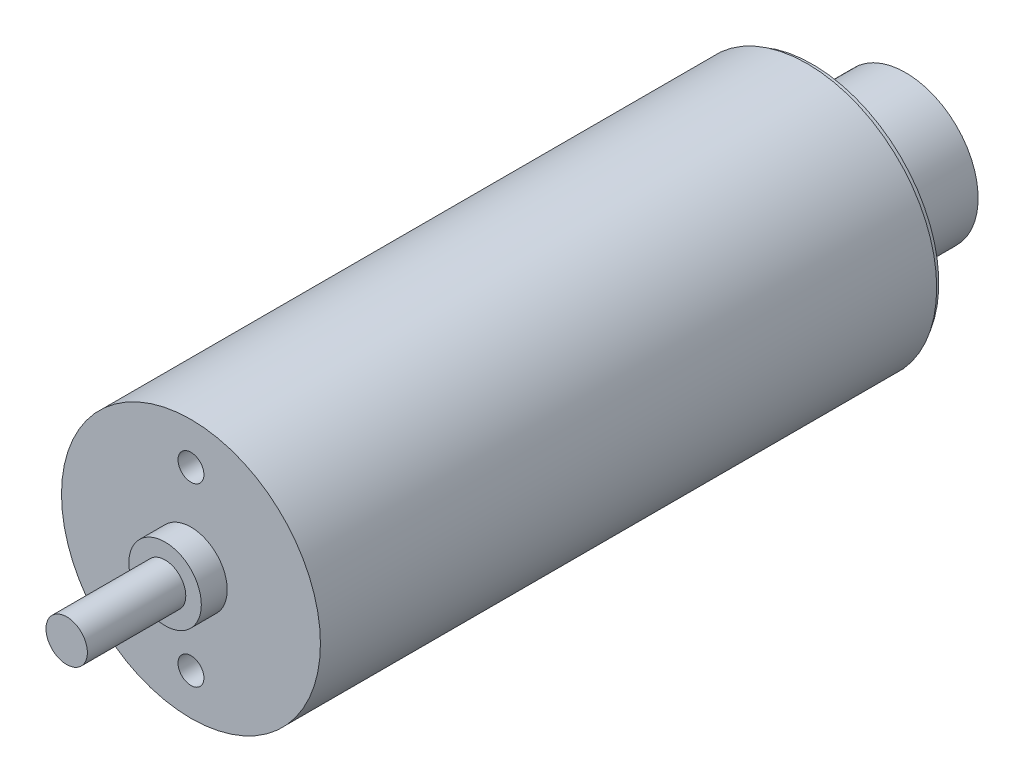
SolidWorks part; units mm, degrees
material "AISI 304"
ref_plane "Front Plane" through (0, 0, 0) normal (0, 0, 1) x (1, 0, 0)
ref_plane "Top Plane" through (0, 0, 0) normal (0, 1, 0) x (1, 0, 0)
ref_plane "Right Plane" through (0, 0, 0) normal (1, 0, 0) x (0, 0, -1)
sketch "Sketch1" plane through (0, 0, 0) normal (0, 0, 1) x (1, 0, 0)
  circle A0 centre (0, 0) radius 12.5
  dimension "D1" = 25
extrude "Boss-Extrude1" add sketch "Sketch1" against normal blind 60
sketch "Sketch2" plane through (0, 0, 0) normal (0, 0, 1) x (1, 0, 0)
  circle A0 centre (0, 0) radius 3.5
  circle A1 centre (0, 0) radius 2
  dimension "D1" = 7
  dimension "D2" = 4
extrude "Boss-Extrude2" add sketch "Sketch2" along normal blind 2.5 contours A0 A1 | A1 region at (-3.401, 0, 0)
extrude "Boss-Extrude3" add sketch "Sketch2<3>" along normal blind 12 contours A1 region at (0, 0, 0)
sketch "Sketch2<3>" plane through (0, 0, 0) normal (0, 0, 1) x (1, 0, 0) same geometry as "Sketch2"
hole_wizard "M3x0.5 Tapped Hole1" positions "Sketch3" profile "Sketch4" tap size "M3x0.5" standard "ANSI Metric"
sketch "Sketch3" plane through (0, 0, 0) normal (0, 0, 1) x (1, 0, 0)
  line L0 (0, 8.5) -> (0, -8.5) construction
  point P0 (0, 8.5)
  point P2 (0, -8.5)
  dimension "D1" = 17
cosmetic thread "Hole Thread1" parameters "D1"=59.944, "D2"=3
cosmetic thread "Hole Thread2" parameters "D1"=59.944, "D2"=3
sketch "Sketch4" plane through (0, 8.5, 0) normal (1, 0, 0) x (0, -1, 0)
  line L0 (0, 0) -> (0, 5.7511)
  line L1 (0, 5.7511) -> (1.25, 5)
  line L2 (1.25, 5) -> (1.25, 0)
  line L5 (1.25, 0) -> (0, 0)
  line L10 (0, 5.7511) -> (-1.25, 5) construction
  line L11 (0, -6.35) -> (0, 107.95) construction
  dimension "Tap Drill Dia." = 2.5
  dimension "Tap Drill Depth" = 5
  dimension "Drill Angle" = 118
sketch "Sketch6" plane through (0, 0, -60) normal (0, 0, -1) x (-1, 0, 0)
  circle A0 centre (0, 0) radius 12.2
  circle A1 centre (0, 0) radius 12.5
  circle A2 centre (0, 0) radius 12.5 construction
  dimension "D1" = 24.4
extrude "Cut-Extrude1" cut sketch "Sketch6" against normal blind 0.5
sketch "Sketch5" plane through (0, 0, -60) normal (0, 0, -1) x (-1, 0, 0)
  circle A0 centre (0, 0) radius 7
  dimension "D1" = 14
extrude "Boss-Extrude4" add sketch "Sketch5" along normal blind 9
